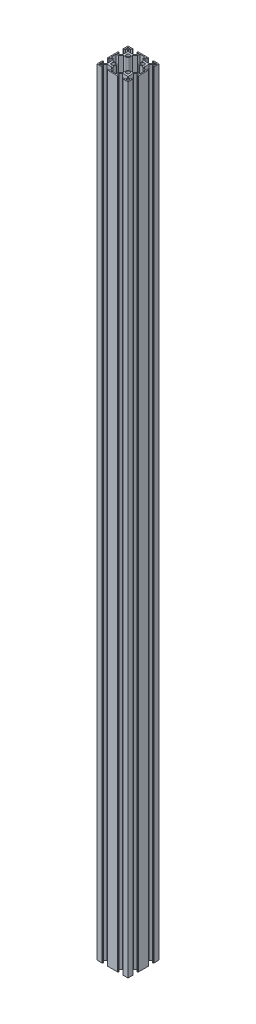
SolidWorks part; units mm, degrees
ref_plane "Front Plane" through (0, 0, 0) normal (0, 0, 1) x (1, 0, 0)
ref_plane "Top Plane" through (0, 0, 0) normal (0, 1, 0) x (1, 0, 0)
ref_plane "Right Plane" through (0, 0, 0) normal (1, 0, 0) x (0, 0, -1)
sketch "Sketch1" plane through (0, 0, 0) normal (0, 1, 0) x (1, 0, 0)
  line L0 (0, 30) -> (0, -30) construction
  line L1 (-30, -30) -> (30, -30)
  line L2 (-30, -30) -> (-30, 30)
  line L3 (-30, 30) -> (30, 30)
  line L4 (30, -30) -> (30, 30)
  line L5 (-30, -30) -> (30, 30) construction
  line L6 (-30, 30) -> (30, -30) construction
  line L7 (-30, 0) -> (30, 0) construction
  line L8 (-23.05, -28) -> (-6.95, -28)
  line L9 (-6.95, -28) -> (-6.95, -24.4)
  line L10 (-6.95, -24.4) -> (-10.615, -20.8)
  line L11 (-10.615, -20.8) -> (-19.385, -20.8)
  line L12 (-19.385, -20.8) -> (-23.05, -24.4)
  line L13 (-23.05, -24.4) -> (-23.05, -28)
  line L14 (10.615, -20.8) -> (19.385, -20.8)
  line L15 (6.95, -24.4) -> (10.615, -20.8)
  line L16 (6.95, -28) -> (6.95, -24.4)
  line L17 (23.05, -28) -> (6.95, -28)
  line L18 (23.05, -24.4) -> (23.05, -28)
  line L19 (19.385, -20.8) -> (23.05, -24.4)
  line L20 (19.385, 20.8) -> (23.05, 24.4)
  line L21 (23.05, 24.4) -> (23.05, 28)
  line L22 (23.05, 28) -> (6.95, 28)
  line L23 (6.95, 28) -> (6.95, 24.4)
  line L24 (6.95, 24.4) -> (10.615, 20.8)
  line L25 (10.615, 20.8) -> (19.385, 20.8)
  line L26 (-23.05, 24.4) -> (-23.05, 28)
  line L27 (-19.385, 20.8) -> (-23.05, 24.4)
  line L28 (-10.615, 20.8) -> (-19.385, 20.8)
  line L29 (-6.95, 24.4) -> (-10.615, 20.8)
  line L30 (-6.95, 28) -> (-6.95, 24.4)
  line L31 (-23.05, 28) -> (-6.95, 28)
  line L32 (-20.8, 19.385) -> (-24.4, 23.05)
  line L33 (-24.4, 23.05) -> (-28, 23.05)
  line L34 (-28, 23.05) -> (-28, 6.95)
  line L35 (-28, 6.95) -> (-24.4, 6.95)
  line L36 (-24.4, 6.95) -> (-20.8, 10.615)
  line L37 (-20.8, 10.615) -> (-20.8, 19.385)
  line L38 (-24.4, -23.05) -> (-28, -23.05)
  line L39 (-20.8, -19.385) -> (-24.4, -23.05)
  line L40 (-20.8, -10.615) -> (-20.8, -19.385)
  line L41 (-24.4, -6.95) -> (-20.8, -10.615)
  line L42 (-28, -6.95) -> (-24.4, -6.95)
  line L43 (-28, -23.05) -> (-28, -6.95)
  line L44 (20.8, -19.385) -> (24.4, -23.05)
  line L45 (24.4, -23.05) -> (28, -23.05)
  line L46 (28, -23.05) -> (28, -6.95)
  line L47 (28, -6.95) -> (24.4, -6.95)
  line L48 (24.4, -6.95) -> (20.8, -10.615)
  line L49 (20.8, -10.615) -> (20.8, -19.385)
  line L50 (24.4, 23.05) -> (28, 23.05)
  line L51 (20.8, 19.385) -> (24.4, 23.05)
  line L52 (20.8, 10.615) -> (20.8, 19.385)
  line L53 (24.4, 6.95) -> (20.8, 10.615)
  line L54 (28, 6.95) -> (24.4, 6.95)
  line L55 (28, 23.05) -> (28, 6.95)
  point P0 (0, 0)
  dimension "D1" = 60
  dimension "D2" = 16.1
  dimension "D3" = 8.77
  dimension "D4" = 3.6
  dimension "D5" = 7.2
  dimension "D6" = 2
  dimension "D7" = 6.95
extrude "Boss-Extrude1" add sketch "Sketch1" along normal blind 1500
sketch "Sketch2" plane through (0, 1500, 0) normal (0, 1, 0) x (1, 0, 0)
  line L0 (-19.1, -28) -> (-19.1, -29)
  line L1 (-23.05, -28) -> (-6.95, -28) construction
  line L2 (-30, -30) -> (30, -30) construction
  line L3 (-10.9, -28) -> (-10.9, -29)
  line L4 (-10.9, -29) -> (-9.9, -29)
  line L5 (-9.9, -29) -> (-9.9, -30)
  line L6 (-19.1, -29) -> (-20.1, -29)
  line L7 (-20.1, -29) -> (-20.1, -30)
  line L8 (-19.1, -28) -> (-10.9, -28)
  line L9 (-20.1, -30) -> (-9.9, -30)
  dimension "D1" = 8.2
  dimension "D2" = 3.95
  dimension "D3" = 1
  dimension "D4" = 1
extrude "Cut-Extrude1" cut sketch "Sketch2" against normal through all
mirror "Mirror1" about plane through (0, 0, 0) normal (1, 0, 0) of "Cut-Extrude1"
ref_axis "Axis1" through (0, 1050, 0) along (0, -1, 0)
pattern_circular "CirPattern1" count 4 over 360 about axis through (0, 1050, 0) along (0, -1, 0) of "Cut-Extrude1", "Mirror1"
sketch "Sketch4" plane through (0, 1500, 0) normal (0, 1, 0) x (1, 0, 0)
  line L0 (19.385, 18.8) -> (9.797, 18.8) construction
  line L1 (-18.8, 18.8) -> (-18.8, 9.797)
  line L2 (18.8, -19.385) -> (18.8, -9.797) construction
  line L3 (28, 4.95) -> (28, -4.95)
  line L4 (-18.8, -9.797) -> (-18.8, -19.385) construction
  line L5 (4.95, -28) -> (-4.95, -28)
  line L6 (-9.797, 18.8) -> (-9.797, 13.197)
  line L7 (-28, -4.95) -> (-28, 4.95)
  line L8 (-18.8, 9.797) -> (-23.5611, 4.95)
  line L9 (-23.5611, 4.95) -> (-28, 4.95)
  line L10 (18.8, 18.8) -> (9.797, 18.8)
  line L11 (9.797, 18.8) -> (4.95, 23.5611)
  line L12 (4.95, 23.5611) -> (4.95, 28)
  line L13 (4.95, 28) -> (4.95, 28)
  line L14 (4.95, 28) -> (4.95, 28)
  line L15 (4.95, 28) -> (4.95, 28)
  line L16 (4.95, 28) -> (4.95, 28)
  line L17 (4.95, 28) -> (-4.95, 28)
  line L18 (-4.95, 28) -> (-4.95, 28)
  line L19 (-4.95, 28) -> (-4.95, 28)
  line L20 (-4.95, 28) -> (-4.95, 28)
  line L21 (-4.95, 28) -> (-4.95, 28)
  line L22 (-4.95, 28) -> (-4.95, 23.5611)
  line L23 (-4.95, 23.5611) -> (-9.797, 18.8)
  line L24 (-9.797, 18.8) -> (-18.8, 18.8)
  line L25 (28, 4.95) -> (23.5611, 4.95)
  line L26 (23.5611, 4.95) -> (18.8, 9.797)
  line L27 (18.8, 9.797) -> (18.8, 18.8)
  line L28 (18.8, -18.8) -> (18.8, -9.797)
  line L29 (18.8, -9.797) -> (23.5611, -4.95)
  line L30 (23.5611, -4.95) -> (28, -4.95)
  line L31 (4.95, -28) -> (4.95, -23.5611)
  line L32 (4.95, -23.5611) -> (9.797, -18.8)
  line L33 (9.797, -18.8) -> (18.8, -18.8)
  line L34 (-18.8, -18.8) -> (-9.797, -18.8)
  line L35 (-9.797, -18.8) -> (-4.95, -23.5611)
  line L36 (-4.95, -23.5611) -> (-4.95, -28)
  line L37 (-28, -4.95) -> (-23.5611, -4.95)
  line L38 (-23.5611, -4.95) -> (-18.8, -9.797)
  line L39 (-18.8, -9.797) -> (-18.8, -18.8)
  line L40 (-9.797, 18.8) -> (-19.385, 18.8) construction
  line L41 (-18.8, 19.385) -> (-18.8, 9.797) construction
  line L42 (18.8, 9.797) -> (18.8, 19.385) construction
  line L43 (9.797, -18.8) -> (19.385, -18.8) construction
  line L44 (-19.385, -18.8) -> (-9.797, -18.8) construction
  line L45 (-13.197, 9.797) -> (-18.8, 9.797)
  line L46 (9.797, 18.8) -> (9.797, 13.197)
  line L47 (13.197, 9.797) -> (18.8, 9.797)
  line L48 (-18.8, -9.797) -> (-13.197, -9.797)
  line L49 (-9.797, -13.197) -> (-9.797, -18.8)
  line L50 (9.797, -18.8) -> (9.797, -13.197)
  line L51 (13.197, -9.797) -> (18.8, -9.797)
  line L52 (-27.5, -28) -> (-24.9, -28)
  line L53 (24.9, -28) -> (27.5, -28)
  line L54 (24.4, -27.5) -> (24.4, -24.9)
  line L55 (24.9, -24.4) -> (27.5, -24.4)
  line L56 (28, -27.5) -> (28, -24.9)
  line L57 (24.4, -28) -> (28, -24.4) construction
  line L58 (24.4, -24.4) -> (28, -28) construction
  line L59 (-28, -24.9) -> (-28, -27.5)
  line L60 (-27.5, -24.4) -> (-24.9, -24.4)
  line L61 (-24.4, -24.9) -> (-24.4, -27.5)
  line L62 (-28, 27.5) -> (-28, 24.9)
  line L63 (-24.9, 28) -> (-27.5, 28)
  line L64 (-24.4, 27.5) -> (-24.4, 24.9)
  line L65 (-24.9, 24.4) -> (-27.5, 24.4)
  line L66 (27.5, 28) -> (24.9, 28)
  line L67 (28, 24.9) -> (28, 27.5)
  line L68 (27.5, 24.4) -> (24.9, 24.4)
  line L69 (24.4, 24.9) -> (24.4, 27.5)
  line L116 (28, 19.1) -> (29, 19.1)
  line L117 (29, 19.1) -> (29, 20.1)
  line L118 (29, 20.1) -> (30, 20.1)
  line L119 (30, 20.1) -> (30, 30)
  line L120 (30, 30) -> (20.1, 30)
  line L121 (20.1, 30) -> (20.1, 29)
  line L122 (20.1, 29) -> (19.1, 29)
  line L123 (19.1, 29) -> (19.1, 28)
  line L124 (19.1, 28) -> (23.05, 28)
  line L125 (23.05, 28) -> (23.05, 24.4)
  line L126 (23.05, 24.4) -> (19.385, 20.8)
  line L127 (19.385, 20.8) -> (10.615, 20.8)
  line L128 (10.615, 20.8) -> (6.95, 24.4)
  line L129 (6.95, 24.4) -> (6.95, 28)
  line L130 (6.95, 28) -> (10.9, 28)
  line L131 (10.9, 28) -> (10.9, 29)
  line L132 (10.9, 29) -> (9.9, 29)
  line L133 (9.9, 29) -> (9.9, 30)
  line L134 (9.9, 30) -> (-9.9, 30)
  line L135 (-9.9, 30) -> (-9.9, 29)
  line L136 (-9.9, 29) -> (-10.9, 29)
  line L137 (-10.9, 29) -> (-10.9, 28)
  line L138 (-10.9, 28) -> (-6.95, 28)
  line L139 (-6.95, 28) -> (-6.95, 24.4)
  line L140 (-6.95, 24.4) -> (-10.615, 20.8)
  line L141 (-10.615, 20.8) -> (-19.385, 20.8)
  line L142 (-19.385, 20.8) -> (-23.05, 24.4)
  line L143 (-23.05, 24.4) -> (-23.05, 28)
  line L144 (-23.05, 28) -> (-19.1, 28)
  line L145 (-19.1, 28) -> (-19.1, 29)
  line L146 (-19.1, 29) -> (-20.1, 29)
  line L147 (-20.1, 29) -> (-20.1, 30)
  line L148 (-20.1, 30) -> (-30, 30)
  line L149 (-30, 30) -> (-30, 20.1)
  line L150 (-30, 20.1) -> (-29, 20.1)
  line L151 (-29, 20.1) -> (-29, 19.1)
  line L152 (-29, 19.1) -> (-28, 19.1)
  line L153 (-28, 19.1) -> (-28, 23.05)
  line L154 (-28, 23.05) -> (-24.4, 23.05)
  line L155 (-24.4, 23.05) -> (-20.8, 19.385)
  line L156 (-20.8, 19.385) -> (-20.8, 10.615)
  line L157 (-20.8, 10.615) -> (-24.4, 6.95)
  line L158 (-24.4, 6.95) -> (-28, 6.95)
  line L159 (-28, 6.95) -> (-28, 10.9)
  line L160 (-28, 10.9) -> (-29, 10.9)
  line L161 (-29, 10.9) -> (-29, 9.9)
  line L162 (-29, 9.9) -> (-30, 9.9)
  line L163 (-30, 9.9) -> (-30, -9.9)
  line L164 (-30, -9.9) -> (-29, -9.9)
  line L165 (-29, -9.9) -> (-29, -10.9)
  line L166 (-29, -10.9) -> (-28, -10.9)
  line L167 (-28, -10.9) -> (-28, -6.95)
  line L168 (-28, -6.95) -> (-24.4, -6.95)
  line L169 (-24.4, -6.95) -> (-20.8, -10.615)
  line L170 (-20.8, -10.615) -> (-20.8, -19.385)
  line L171 (-20.8, -19.385) -> (-24.4, -23.05)
  line L172 (-24.4, -23.05) -> (-28, -23.05)
  line L173 (-28, -23.05) -> (-28, -19.1)
  line L174 (-28, -19.1) -> (-29, -19.1)
  line L175 (-29, -19.1) -> (-29, -20.1)
  line L176 (-29, -20.1) -> (-30, -20.1)
  line L177 (-30, -20.1) -> (-30, -30)
  line L178 (-30, -30) -> (-20.1, -30)
  line L179 (-20.1, -30) -> (-20.1, -29)
  line L180 (-20.1, -29) -> (-19.1, -29)
  line L181 (-19.1, -29) -> (-19.1, -28)
  line L182 (-19.1, -28) -> (-23.05, -28)
  line L183 (-23.05, -28) -> (-23.05, -24.4)
  line L184 (-23.05, -24.4) -> (-19.385, -20.8)
  line L185 (-19.385, -20.8) -> (-10.615, -20.8)
  line L186 (-10.615, -20.8) -> (-6.95, -24.4)
  line L187 (-6.95, -24.4) -> (-6.95, -28)
  line L188 (-6.95, -28) -> (-10.9, -28)
  line L189 (-10.9, -28) -> (-10.9, -29)
  line L190 (-10.9, -29) -> (-9.9, -29)
  line L191 (-9.9, -29) -> (-9.9, -30)
  line L192 (-9.9, -30) -> (9.9, -30)
  line L193 (9.9, -30) -> (9.9, -29)
  line L194 (9.9, -29) -> (10.9, -29)
  line L195 (10.9, -29) -> (10.9, -28)
  line L196 (10.9, -28) -> (6.95, -28)
  line L197 (6.95, -28) -> (6.95, -24.4)
  line L198 (6.95, -24.4) -> (10.615, -20.8)
  line L199 (10.615, -20.8) -> (19.385, -20.8)
  line L200 (19.385, -20.8) -> (23.05, -24.4)
  line L201 (23.05, -24.4) -> (23.05, -28)
  line L202 (23.05, -28) -> (19.1, -28)
  line L203 (19.1, -28) -> (19.1, -29)
  line L204 (19.1, -29) -> (20.1, -29)
  line L205 (20.1, -29) -> (20.1, -30)
  line L206 (20.1, -30) -> (30, -30)
  line L207 (30, -30) -> (30, -20.1)
  line L208 (30, -20.1) -> (29, -20.1)
  line L209 (29, -20.1) -> (29, -19.1)
  line L210 (29, -19.1) -> (28, -19.1)
  line L211 (28, -19.1) -> (28, -23.05)
  line L212 (28, -23.05) -> (24.4, -23.05)
  line L213 (24.4, -23.05) -> (20.8, -19.385)
  line L214 (20.8, -19.385) -> (20.8, -10.615)
  line L215 (20.8, -10.615) -> (24.4, -6.95)
  line L216 (24.4, -6.95) -> (28, -6.95)
  line L217 (28, -6.95) -> (28, -10.9)
  line L218 (28, -10.9) -> (29, -10.9)
  line L219 (29, -10.9) -> (29, -9.9)
  line L220 (29, -9.9) -> (30, -9.9)
  line L221 (30, -9.9) -> (30, 9.9)
  line L222 (30, 9.9) -> (29, 9.9)
  line L223 (29, 9.9) -> (29, 10.9)
  line L224 (29, 10.9) -> (28, 10.9)
  line L225 (28, 10.9) -> (28, 6.95)
  line L226 (28, 6.95) -> (24.4, 6.95)
  line L227 (24.4, 6.95) -> (20.8, 10.615)
  line L228 (20.8, 10.615) -> (20.8, 19.385)
  line L229 (20.8, 19.385) -> (24.4, 23.05)
  line L230 (24.4, 23.05) -> (28, 23.05)
  line L231 (28, 23.05) -> (28, 19.1)
  line L232 (28, 19.1) -> (29, 19.1)
  line L233 (29, 19.1) -> (29, 20.1)
  line L234 (29, 20.1) -> (30, 20.1)
  line L235 (30, 20.1) -> (30, 30)
  line L236 (30, 30) -> (20.1, 30)
  line L237 (20.1, 30) -> (20.1, 29)
  line L238 (20.1, 29) -> (19.1, 29)
  line L239 (19.1, 29) -> (19.1, 28)
  line L240 (19.1, 28) -> (23.05, 28)
  line L241 (23.05, 28) -> (23.05, 24.4)
  line L242 (23.05, 24.4) -> (19.385, 20.8)
  line L243 (19.385, 20.8) -> (10.615, 20.8)
  line L244 (10.615, 20.8) -> (6.95, 24.4)
  line L245 (6.95, 24.4) -> (6.95, 28)
  line L246 (6.95, 28) -> (10.9, 28)
  line L247 (10.9, 28) -> (10.9, 29)
  line L248 (10.9, 29) -> (9.9, 29)
  line L249 (9.9, 29) -> (9.9, 30)
  line L250 (9.9, 30) -> (-9.9, 30)
  line L251 (-9.9, 30) -> (-9.9, 29)
  line L252 (-9.9, 29) -> (-10.9, 29)
  line L253 (-10.9, 29) -> (-10.9, 28)
  line L254 (-10.9, 28) -> (-6.95, 28)
  line L255 (-6.95, 28) -> (-6.95, 24.4)
  line L256 (-6.95, 24.4) -> (-10.615, 20.8)
  line L257 (-10.615, 20.8) -> (-19.385, 20.8)
  line L258 (-19.385, 20.8) -> (-23.05, 24.4)
  line L259 (-23.05, 24.4) -> (-23.05, 28)
  line L260 (-23.05, 28) -> (-19.1, 28)
  line L261 (-19.1, 28) -> (-19.1, 29)
  line L262 (-19.1, 29) -> (-20.1, 29)
  line L263 (-20.1, 29) -> (-20.1, 30)
  line L264 (-20.1, 30) -> (-30, 30)
  line L265 (-30, 30) -> (-30, 20.1)
  line L266 (-30, 20.1) -> (-29, 20.1)
  line L267 (-29, 20.1) -> (-29, 19.1)
  line L268 (-29, 19.1) -> (-28, 19.1)
  line L269 (-28, 19.1) -> (-28, 23.05)
  line L270 (-28, 23.05) -> (-24.4, 23.05)
  line L271 (-24.4, 23.05) -> (-20.8, 19.385)
  line L272 (-20.8, 19.385) -> (-20.8, 10.615)
  line L273 (-20.8, 10.615) -> (-24.4, 6.95)
  line L274 (-24.4, 6.95) -> (-28, 6.95)
  line L275 (-28, 6.95) -> (-28, 10.9)
  line L276 (-28, 10.9) -> (-29, 10.9)
  line L277 (-29, 10.9) -> (-29, 9.9)
  line L278 (-29, 9.9) -> (-30, 9.9)
  line L279 (-30, 9.9) -> (-30, -9.9)
  line L280 (-30, -9.9) -> (-29, -9.9)
  line L281 (-29, -9.9) -> (-29, -10.9)
  line L282 (-29, -10.9) -> (-28, -10.9)
  line L283 (-28, -10.9) -> (-28, -6.95)
  line L284 (-28, -6.95) -> (-24.4, -6.95)
  line L285 (-24.4, -6.95) -> (-20.8, -10.615)
  line L286 (-20.8, -10.615) -> (-20.8, -19.385)
  line L287 (-20.8, -19.385) -> (-24.4, -23.05)
  line L288 (-24.4, -23.05) -> (-28, -23.05)
  line L289 (-28, -23.05) -> (-28, -19.1)
  line L290 (-28, -19.1) -> (-29, -19.1)
  line L291 (-29, -19.1) -> (-29, -20.1)
  line L292 (-29, -20.1) -> (-30, -20.1)
  line L293 (-30, -20.1) -> (-30, -30)
  line L294 (-30, -30) -> (-20.1, -30)
  line L295 (-20.1, -30) -> (-20.1, -29)
  line L296 (-20.1, -29) -> (-19.1, -29)
  line L297 (-19.1, -29) -> (-19.1, -28)
  line L298 (-19.1, -28) -> (-23.05, -28)
  line L299 (-23.05, -28) -> (-23.05, -24.4)
  line L300 (-23.05, -24.4) -> (-19.385, -20.8)
  line L301 (-19.385, -20.8) -> (-10.615, -20.8)
  line L302 (-10.615, -20.8) -> (-6.95, -24.4)
  line L303 (-6.95, -24.4) -> (-6.95, -28)
  line L304 (-6.95, -28) -> (-10.9, -28)
  line L305 (-10.9, -28) -> (-10.9, -29)
  line L306 (-10.9, -29) -> (-9.9, -29)
  line L307 (-9.9, -29) -> (-9.9, -30)
  line L308 (-9.9, -30) -> (9.9, -30)
  line L309 (9.9, -30) -> (9.9, -29)
  line L310 (9.9, -29) -> (10.9, -29)
  line L311 (10.9, -29) -> (10.9, -28)
  line L312 (10.9, -28) -> (6.95, -28)
  line L313 (6.95, -28) -> (6.95, -24.4)
  line L314 (6.95, -24.4) -> (10.615, -20.8)
  line L315 (10.615, -20.8) -> (19.385, -20.8)
  line L316 (19.385, -20.8) -> (23.05, -24.4)
  line L317 (23.05, -24.4) -> (23.05, -28)
  line L318 (23.05, -28) -> (19.1, -28)
  line L319 (19.1, -28) -> (19.1, -29)
  line L320 (19.1, -29) -> (20.1, -29)
  line L321 (20.1, -29) -> (20.1, -30)
  line L322 (20.1, -30) -> (30, -30)
  line L323 (30, -30) -> (30, -20.1)
  line L324 (30, -20.1) -> (29, -20.1)
  line L325 (29, -20.1) -> (29, -19.1)
  line L326 (29, -19.1) -> (28, -19.1)
  line L327 (28, -19.1) -> (28, -23.05)
  line L328 (28, -23.05) -> (24.4, -23.05)
  line L329 (24.4, -23.05) -> (20.8, -19.385)
  line L330 (20.8, -19.385) -> (20.8, -10.615)
  line L331 (20.8, -10.615) -> (24.4, -6.95)
  line L332 (24.4, -6.95) -> (28, -6.95)
  line L333 (28, -6.95) -> (28, -10.9)
  line L334 (28, -10.9) -> (29, -10.9)
  line L335 (29, -10.9) -> (29, -9.9)
  line L336 (29, -9.9) -> (30, -9.9)
  line L337 (30, -9.9) -> (30, 9.9)
  line L338 (30, 9.9) -> (29, 9.9)
  line L339 (29, 9.9) -> (29, 10.9)
  line L340 (29, 10.9) -> (28, 10.9)
  line L341 (28, 10.9) -> (28, 6.95)
  line L342 (28, 6.95) -> (24.4, 6.95)
  line L343 (24.4, 6.95) -> (20.8, 10.615)
  line L344 (20.8, 10.615) -> (20.8, 19.385)
  line L345 (20.8, 19.385) -> (24.4, 23.05)
  line L346 (24.4, 23.05) -> (28, 23.05)
  line L347 (28, 23.05) -> (28, 19.1)
  circle A0 centre (14.2985, 14.2985) radius 3.4
  arc A1 (13.197, -9.797) -> (9.797, -13.197) centre (13.197, -13.197) ccw
  arc A2 (-9.797, -13.197) -> (-13.197, -9.797) centre (-13.197, -13.197) ccw
  arc A3 (13.197, 9.797) -> (9.797, 13.197) centre (13.197, 13.197) cw
  arc A4 (-9.797, 13.197) -> (-13.197, 9.797) centre (-13.197, 13.197) cw
  circle A5 centre (14.2985, -14.2985) radius 3.4
  circle A6 centre (-14.2985, -14.2985) radius 3.4
  circle A7 centre (-14.2985, 14.2985) radius 3.4
  arc A8 (24.4, -27.5) -> (24.9, -28) centre (24.9, -27.5) ccw
  arc A9 (28, -27.5) -> (27.5, -28) centre (27.5, -27.5) cw
  arc A10 (28, -24.9) -> (27.5, -24.4) centre (27.5, -24.9) ccw
  arc A11 (24.4, -24.9) -> (24.9, -24.4) centre (24.9, -24.9) cw
  arc A12 (-27.5, -28) -> (-28, -27.5) centre (-27.5, -27.5) cw
  arc A13 (-27.5, -24.4) -> (-28, -24.9) centre (-27.5, -24.9) ccw
  arc A14 (-24.9, -24.4) -> (-24.4, -24.9) centre (-24.9, -24.9) cw
  arc A15 (-24.9, -28) -> (-24.4, -27.5) centre (-24.9, -27.5) ccw
  arc A16 (-28, 27.5) -> (-27.5, 28) centre (-27.5, 27.5) cw
  arc A17 (-24.4, 27.5) -> (-24.9, 28) centre (-24.9, 27.5) ccw
  arc A18 (-24.4, 24.9) -> (-24.9, 24.4) centre (-24.9, 24.9) cw
  arc A19 (-28, 24.9) -> (-27.5, 24.4) centre (-27.5, 24.9) ccw
  arc A20 (27.5, 28) -> (28, 27.5) centre (27.5, 27.5) cw
  arc A21 (27.5, 24.4) -> (28, 24.9) centre (27.5, 24.9) ccw
  arc A22 (24.9, 24.4) -> (24.4, 24.9) centre (24.9, 24.9) cw
  arc A23 (24.9, 28) -> (24.4, 27.5) centre (24.9, 27.5) ccw
  point P102 (26.2, -26.2)
  point P104 (14.2985, 18.8)
  point P106 (18.8, 14.2985)
  point P140 (0, 0)
  point P239 (0, 0)
  dimension "D3" = 6.8
  dimension "D4" = 3.4
  dimension "D6" = 0.5
  dimension "D1" = 0
  dimension "D2" = 2
  dimension "D5" = 4
  dimension "D7" = 4
extrude "Cut-Extrude2" cut sketch "Sketch4" against normal through all contours L6 A4 L45 L8 L9 L7 L37 L38 L48 A2 L49 L35 L36 L5 L31 L32 L50 A1 L51 L29 L30 L3 L25 L26 L47 A3 L46 L11 L12 L17 L22 L23 | A7 | A0 | L66 A23 L69 A22 L68 A21 L67 A20 | L62 A19 L65 A18 L64 A17 L63 A16 | L52 A15 L61 A14 L60 A13 L59 A12 | A11 L54 A8 L53 A9 L56 A10 L55 | A6 | A5 region at (0, 1500, 0) region at (-26.2, 1500, 26.2) region at (26.2, 1500, 26.2) region at (-26.2, 1500, -26.2) region at (26.2, 1500, -26.2) region at (14.2985, 1500, -14.2985) region at (-14.2985, 1500, -14.2985)
fillet "Fillet1" radius 0.2 16 edges at (28, 750, -19.1) (30, 750, -20.1) (29, 750, -20.1) (29, 750, -19.1) (28, 750, 10.9) (29, 750, 9.9) (28, 750, 19.1) (29, 750, 20.1) (30, 750, 20.1) (29, 750, 19.1) (29, 750, 10.9) (30, 750, 9.9) (30, 750, -9.9) (29, 750, -9.9) (29, 750, -10.9) (28, 750, -10.9)
fillet "Fillet2" radius 0.2 20 edges at (-20.1, 0, -29.5) (-20.1, 1500, -29.5) (-20.1, 750, -29) (-19.6, 0, -29) (-19.1, 750, -29) (-19.6, 1500, -29) (-9.9, 750, -30) (-10.9, 750, -28) (-10.9, 750, -29) (-9.9, 750, -29) (19.1, 750, -28) (19.1, 750, -29) (20.1, 750, -29) (20.1, 750, -30) (10.9, 750, -28) (10.9, 750, -29) (9.9, 750, -29) (9.9, 750, -30) (-19.1, 750, -28) (-20.1, 750, -30)
fillet "Fillet3" radius 0.2 14 edges at (-29, 750, 9.9) (-29, 750, -20.1) (-30, 750, -20.1) (-29, 750, -19.1) (-28, 750, -10.9) (-29, 750, -10.9) (-29, 750, -9.9) (-30, 750, -9.9) (-29, 750, 10.9) (-30, 750, 9.9) (-28, 750, 19.1) (-29, 750, 19.1) (-29, 750, 20.1) (-30, 750, 20.1)
fillet "Fillet4" radius 0.2 16 edges at (-19.1, 750, 28) (10.9, 750, 28) (19.1, 750, 28) (20.1, 750, 29) (-10.9, 750, 28) (-9.9, 750, 29) (9.9, 750, 29) (-20.1, 750, 29) (19.1, 750, 29) (20.1, 750, 30) (10.9, 750, 29) (9.9, 750, 30) (-9.9, 750, 30) (-10.9, 750, 29) (-19.1, 750, 29) (-20.1, 750, 30)
